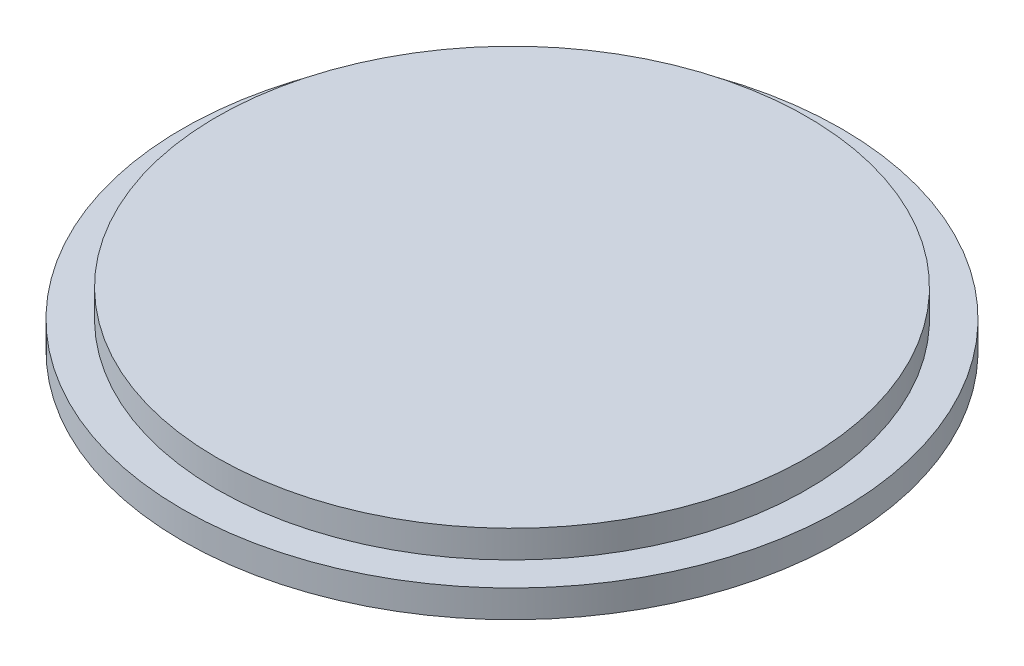
SolidWorks part; units mm, degrees
ref_plane "Alzado" through (0, 0, 0) normal (0, 0, 1) x (1, 0, 0)
ref_plane "Planta" through (0, 0, 0) normal (0, 1, 0) x (1, 0, 0)
ref_plane "Vista lateral" through (0, 0, 0) normal (1, 0, 0) x (0, 0, -1)
sketch "Croquis1" plane through (0, 0, 0) normal (0, 1, 0) x (1, 0, 0)
  circle A0 centre (0, 0) radius 10.75
  circle A1 centre (0, 0) radius 12
  dimension "D1" = 21.5
  dimension "D2" = 1.25
extrude "Saliente-Extruir1" add sketch "Croquis1" along normal blind 1
extrude "Saliente-Extruir2" add sketch "Croquis1<2>" along normal blind 2 contours A0 region at (0, 0, 0)
sketch "Croquis1<2>" plane through (0, 0, 0) normal (0, 1, 0) x (1, 0, 0) same geometry as "Croquis1"
